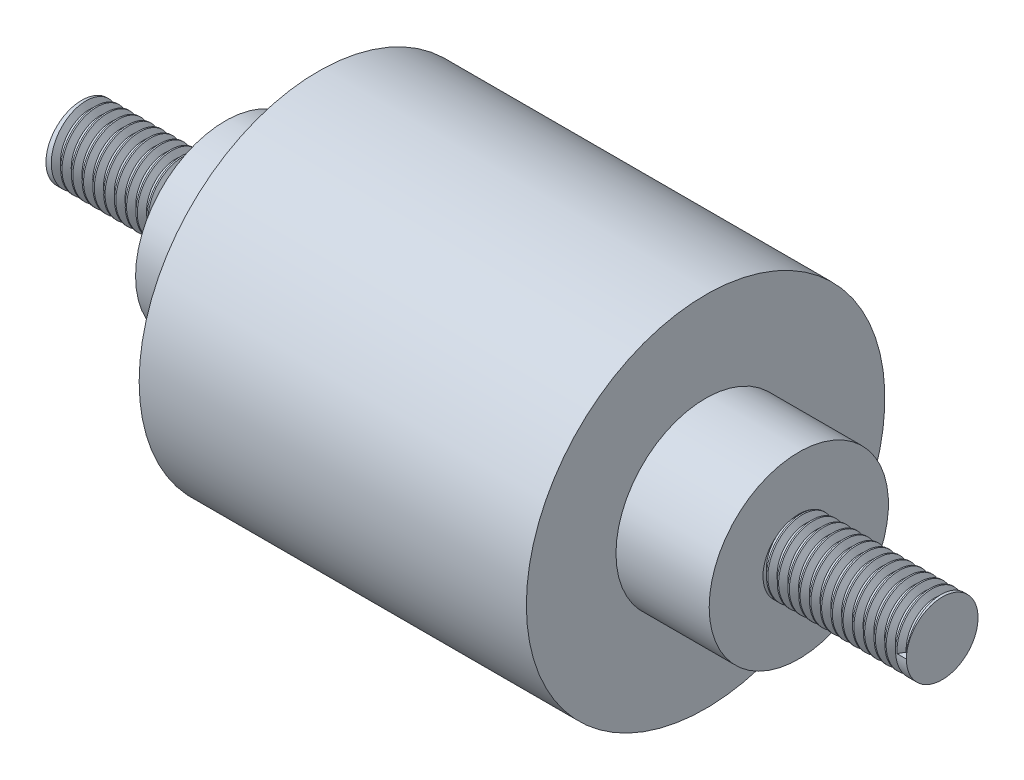
SolidWorks part; units mm, degrees
ref_plane "Front Plane" through (0, 0, 0) normal (0, 0, 1) x (1, 0, 0)
ref_plane "Top Plane" through (0, 0, 0) normal (0, 1, 0) x (1, 0, 0)
ref_plane "Right Plane" through (0, 0, 0) normal (1, 0, 0) x (0, 0, -1)
sketch "Sketch1" plane through (0, 0, 0) normal (0, 0, 1) x (1, 0, 0)
  line L0 (0, -64.1686) -> (0, 56.0058) construction
  line L1 (43.9884, 0) -> (-105.0581, 0) construction
  line L2 (-40, 0) -> (-40, 12.5)
  line L3 (-40, 12.5) -> (-27, 12.5)
  line L4 (-27, 12.5) -> (-27, 25)
  line L5 (-27, 25) -> (27, 25)
  line L6 (-40, 0) -> (40, 0)
  line L7 (40, 0) -> (40, 12.5)
  line L8 (40, 12.5) -> (27, 12.5)
  line L9 (27, 12.5) -> (27, 25)
  dimension "D1" = 13
  dimension "D2" = 25
  dimension "D3" = 54
  dimension "D4" = 50
revolve "Revolve1" add sketch "Sketch1" angle 360 about L6
sketch "Sketch2" plane through (40, 0, 0) normal (1, 0, 0) x (0, 0, -1)
  circle A0 centre (0, 0) radius 5
  dimension "D1" = 10
extrude "Boss-Extrude1" add sketch "Sketch2" along normal blind 20
thread "Thread1" pitch 1.5 method cut profile "Thread Profile1" start angle 0, offset 0, length 0, pitch 1.5, diameter 10
ref_plane "Plane1" through (60, 0, 5) normal (0, -1, 0) x (0, 0, 1)
sketch "Thread Profile1" plane through (60, 0, 5) normal (0, -1, 0) x (0, 0, 1)
  line L0 (0, 0) -> (0, 1.5) construction
  line L11 (0, 0) -> (0, 1.3125)
  line L12 (0, 1.3125) -> (-0.8119, 0.8437)
  line L13 (-0.8119, 0.8437) -> (-0.8119, 0.4687)
  line L15 (-0.8119, 0.4687) -> (0, 0)
  line L17 (-0.8119, 0.6562) -> (0, 0.6562) construction
  point P2 (0, 0)
  dimension "Pitch" = 1.5
  dimension "Profile_Angle" = 60
  dimension "Profile_Land" = 0.375
  dimension "Profile_Height" = 0.8119
mirror "Mirror3" about plane through (0, 0, 0) normal (1, 0, 0) of "Boss-Extrude1"
thread "Thread2" pitch 1.5 method cut profile "Thread Profile2" start angle 0, offset 0, length 0, pitch 1.5, diameter 10
ref_plane "Plane2" through (-60, 0, -5) normal (0, -1, 0) x (0, 0, -1)
sketch "Thread Profile2" plane through (-60, 0, -5) normal (0, -1, 0) x (0, 0, -1)
  line L0 (0, 0) -> (0, 1.5) construction
  line L11 (0, 0) -> (0, 1.3125)
  line L12 (0, 1.3125) -> (-0.8119, 0.8437)
  line L13 (-0.8119, 0.8437) -> (-0.8119, 0.4687)
  line L15 (-0.8119, 0.4687) -> (0, 0)
  line L17 (-0.8119, 0.6562) -> (0, 0.6562) construction
  point P2 (0, 0)
  dimension "Pitch" = 1.5
  dimension "Profile_Angle" = 60
  dimension "Profile_Land" = 0.375
  dimension "Profile_Height" = 0.8119
